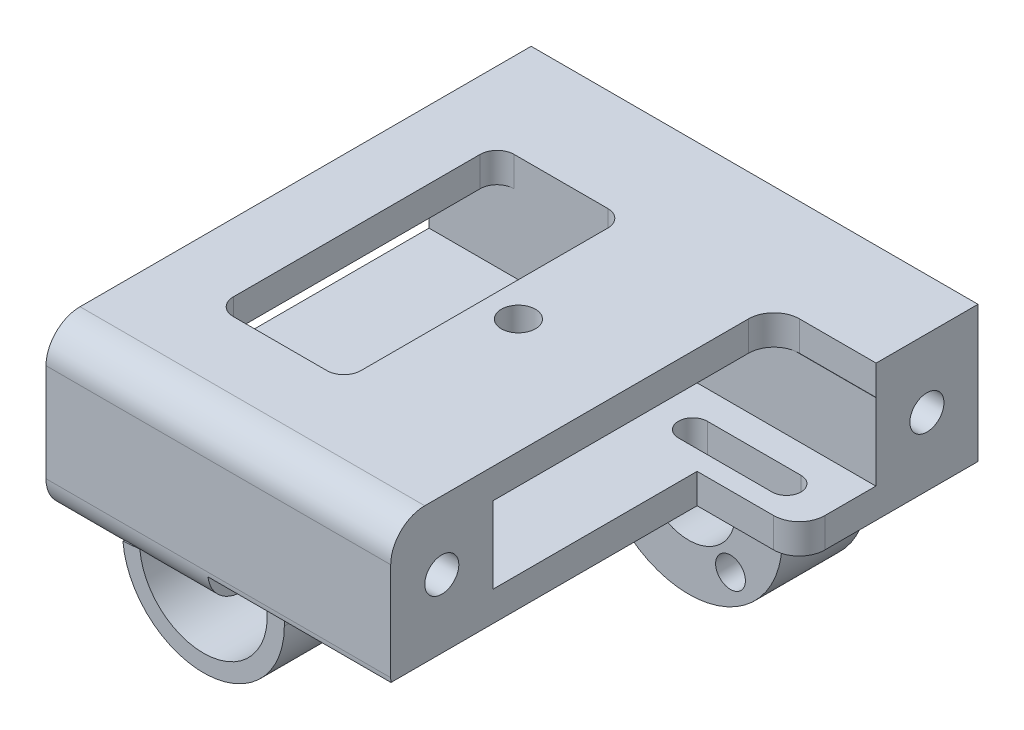
SolidWorks part; units mm, degrees
ref_plane "Front Plane" through (0, 0, 0) normal (0, 0, 1) x (1, 0, 0)
ref_plane "Top Plane" through (0, 0, 0) normal (0, 1, 0) x (1, 0, 0)
ref_plane "Right Plane" through (0, 0, 0) normal (1, 0, 0) x (0, 0, -1)
sketch "Sketch1" plane through (0, 0, 0) normal (0, 0, 1) x (1, 0, 0)
  line L0 (0, 0) -> (0, -35)
  line L1 (0, -35) -> (19, -35)
  line L2 (19, -35) -> (19, -16)
  line L3 (19, -16) -> (52.5, -16)
  line L4 (52.5, -16) -> (52.5, 0)
  line L5 (52.5, 0) -> (0, 0)
  line L6 (0, 0) -> (0.6966, -0.1385)
  dimension "D1" = 35
  dimension "D2" = 19
  dimension "D3" = 52.5
  dimension "D4" = 16
extrude "Boss-Extrude1" add sketch "Sketch1" along normal blind 57 contours L4 L5 L0 L1 L2 L3 region at (21.2152, -13.2602, 0)
ref_plane "Plane1" through (0, 0, 50) normal (0, 0, 1) x (1, 0, 0)
sketch "Sketch3" plane through (0, 0, 0) normal (-1, 0, 0) x (0, 0, 1)
  line L0 (57, 0) -> (0, 0) construction
  line L1 (12, -3.5) -> (45, -3.5)
  line L2 (12, -3.5) -> (12, -12.5)
  line L3 (12, -12.5) -> (45, -12.5)
  line L4 (45, -3.5) -> (45, -12.5)
  line L5 (57, -35) -> (48, -35)
  line L6 (57, -35) -> (57, -19.5)
  line L7 (57, -19.5) -> (48, -19.5)
  line L8 (48, -35) -> (48, -19.5)
  line L9 (0, 0) -> (0, -35) construction
  line L14 (57, -35) -> (0, -35) construction
  dimension "D1" = 9
  dimension "D2" = 33
  dimension "D3" = 3.5
  dimension "D4" = 12
  dimension "D5" = 15.5
  dimension "D6" = 9
extrude "Cut-Extrude2" cut sketch "Sketch3" against normal through all
fillet "Fillet1" radius 4 2 edges at (26.25, 0, 57) (9.5, -19.5, 57)
sketch "Sketch4" plane through (0, 0, 0) normal (0, 0, -1) x (-1, 0, 0)
  line L0 (-9.5, -25.5) -> (-9.5, -35) construction
  line L1 (0, -35) -> (-19, -35) construction
  line L2 (-2.0103, -25.1075) -> (-0.013, -25.0028)
  line L3 (0, -35) -> (-19, -35)
  line L4 (0, -35) -> (0, -16)
  line L5 (0, -16) -> (-19, -16)
  line L6 (-19, -35) -> (-19, -16)
  line L7 (-2.0285, -26.1537) -> (-0.0362, -26.328)
  line L8 (-2.0285, -26.1537) -> (-9.5, -25.5) construction
  line L9 (-0.013, -25.0028) -> (0, -25.0021)
  circle A0 centre (-9.5, -25.5) radius 7.5
  circle A1 centre (-9.5, -25.5) radius 9.5
  line M8 (-19, -35) -> (0, -35)
  line M9 (0, -35) -> (0, 0)
  dimension "D1" = 15
  dimension "D2" = 19
  dimension "D3" = 8
  dimension "D4" = 85
extrude "Cut-Extrude3" cut sketch "Sketch4" against normal through all contours A0 | A1 L6 M8 | L7 A1 L2 A0 | A1 L3 M9 | A1 L4 L9 region at (0.969, -25.6489, 0) region at (9.5, -25.5, 0) region at (0.0039, -25.1268, 0) region at (2.122, -32.878, 0) region at (16.878, -32.878, 0)
sketch "Sketch5" plane through (0, -16, 0) normal (0, -1, 0) x (1, 0, 0)
  line L0 (28, 28.5) -> (32, 28.5) construction
  line L1 (22, 45) -> (26, 45) construction
  line L2 (20, 43) -> (20, 14) construction
  line L3 (22, 12) -> (26, 12) construction
  line L4 (28, 43) -> (28, 14) construction
  line L5 (36, 17) -> (47, 17) construction
  line L6 (36, 18.7) -> (47, 18.7)
  line L7 (36, 15.3) -> (47, 15.3)
  line L8 (19, 56.9686) -> (19, 0) construction
  line L10 (19, 0) -> (52.5, 0) construction
  line L11 (52.5, 0) -> (52.5, 18) construction
  line L12 (52.5, 56.9686) -> (52.5, 0) construction
  line L13 (0, 57) -> (52.5, 57) construction
  line L14 (49.5, 18) -> (49.5, 21) construction
  line L15 (49.5, 21) -> (40.5, 21)
  line L16 (40.5, 21) -> (40.5, 57)
  line L18 (40.5, 57) -> (52.5, 57)
  line L19 (52.5, 57) -> (52.5, 18)
  arc A0 (20, 14) -> (22, 12) centre (22, 14) ccw construction
  arc A1 (26, 12) -> (28, 14) centre (26, 14) ccw construction
  arc A2 (28, 43) -> (26, 45) centre (26, 43) ccw construction
  arc A3 (22, 45) -> (20, 43) centre (22, 43) ccw construction
  circle A4 centre (32, 28.5) radius 2 construction
  arc A5 (36, 18.7) -> (36, 15.3) centre (36, 17) ccw
  arc A6 (47, 15.3) -> (47, 18.7) centre (47, 17) ccw
  arc A7 (52.5, 18) -> (49.5, 21) centre (49.5, 18) ccw
  point P17 (41.5, 17)
  line M12 (52.5, 0) -> (52.5, 56.9686)
  dimension "D1" = 2
  dimension "D4" = 4
  dimension "D6" = 1.7
  dimension "D9" = 2.3
  dimension "D12" = 6
  dimension "D2" = 8
  dimension "D3" = 33
  dimension "D5" = 4
  dimension "D7" = 11
  dimension "D8" = 1
  dimension "D10" = 12
  dimension "D11" = 18
  dimension "D13" = 9
  dimension "D14" = 4.5
extrude "Cut-Extrude4" cut sketch "Sketch5" against normal up to surface (12.5 mm away) contours A4 | L7 A6 L6 A5 | A7 L16 L15 M12 | L19 L18 L16 | L2 A0 L3 A1 L4 A2 L1 A3 region at (41.5, -16, 17) region at (46.5237, -16, 38.9169) up to face at (26.25, -3.5, 28.5)
sketch "Sketch6" plane through (0, 0, 0) normal (0, 1, 0) x (1, 0, 0)
  line L0 (52.5, 0) -> (0, 0) construction
  line L1 (10, -12) -> (21, -12)
  line L2 (8, -14) -> (8, -43)
  line L3 (10, -45) -> (21, -45)
  line L4 (23, -14) -> (23, -43)
  line L5 (0, -53) -> (0, 0) construction
  line L6 (52.5, -56.9686) -> (40.5, -56.9686) construction
  line L7 (43.5, -11.9686) -> (52.5, -11.9686)
  line L8 (40.5, -14.9686) -> (40.5, -56.9686)
  line L9 (40.5, -56.9686) -> (52.5, -56.9686)
  line L10 (52.5, -11.9686) -> (52.5, -56.9686)
  line L11 (52.5, -53) -> (52.5, 0) construction
  line L12 (27, -28.5) -> (23, -28.5) construction
  arc A0 (10, -45) -> (8, -43) centre (10, -43) cw
  arc A1 (23, -43) -> (21, -45) centre (21, -43) cw
  arc A2 (23, -14) -> (21, -12) centre (21, -14) ccw
  arc A3 (10, -12) -> (8, -14) centre (10, -14) ccw
  arc A4 (43.5, -11.9686) -> (40.5, -14.9686) centre (43.5, -14.9686) ccw
  circle A5 centre (27, -28.5) radius 2 construction
  point P6 (8, -45)
  point P11 (23, -12)
  point P14 (8, -12)
  point P25 (40.5, -11.9686)
  dimension "D3" = 2
  dimension "D8" = 3
  dimension "D9" = 4
  dimension "D10" = 4
  dimension "D1" = 33
  dimension "D2" = 15
  dimension "D4" = 12
  dimension "D5" = 8
  dimension "D6" = 45
  dimension "D7" = 12
extrude "Cut-Extrude5" cut sketch "Sketch6" against normal up to surface (3.5 mm away) up to face at (31, -3.5, 37.9895)
sketch "Sketch9" plane through (0, -3.5, 0) normal (0, -1, 0) x (1, 0, 0)
  line L0 (40.5, 21) -> (40.5, 56.9686) construction
  line L1 (19, 0) -> (52.5, 0) construction
  circle A0 centre (27, 28.5) radius 3.2
  dimension "D1" = 6.4
  dimension "D2" = 13.5
  dimension "D3" = 28.5
ref_plane "Plane3" through (0, -5, 0) normal (0, -1, 0) x (-1, 0, 0)
sketch "Sketch10" plane through (0, -5, 0) normal (0, -1, 0) x (-1, 0, 0)
  circle A0 centre (-27, -28.5) radius 2.8
  dimension "D1" = 5.6
loft "Loft1" add profiles "Sketch9", "Sketch10" connector at (30.0985, -3.5, 27.7003) connector at (29.7453, -5, 27.9494)
ref_plane "Plane4" through (0, -8, 0) normal (0, -1, 0) x (-1, 0, 0)
mirror "Mirror2" about plane through (0, -8, 0) normal (0, -1, 0) of "Loft1"
sketch "Sketch11" plane through (0, -11, 0) normal (0, 1, 0) x (1, 0, 0)
  circle A0 centre (27, -28.5) radius 2 construction
  circle A1 centre (27, -28.5) radius 2
extrude "Cut-Extrude6" cut sketch "Sketch11" against normal through all both and the other way through all
sketch "Sketch13" plane through (52.5, 0, 0) normal (1, 0, 0) x (0, 0, -1)
  line L0 (-51, -8) -> (-6, -8) construction
  line L1 (-6, -8) -> (0, -8) construction
  line L2 (0, -16) -> (0, 0) construction
  line L3 (-51, -8) -> (-57, -8) construction
  line L4 (-57, -4) -> (-57, -15.5) construction
  circle A0 centre (-6, -8) radius 2
  circle A1 centre (-51, -8) radius 2
  dimension "D1" = 45
  dimension "D2" = 4
extrude "Cut-Extrude7" cut sketch "Sketch13" against normal blind 20
sketch "Sketch14" plane through (0, 0, 0) normal (0, 0, -1) x (-1, 0, 0)
  line L0 (-28.5, -25.5) -> (-9.5, -25.5) construction
  line L1 (-28.5, -25.5) -> (-28.5, -14.5) construction
  line L2 (-23.5747, -19.1959) -> (-33.4253, -31.8041) construction
  line L3 (-34.8041, -20.5747) -> (-22.1959, -30.4253) construction
  line L4 (-28.5, -14.5) -> (-17.5, -14.5)
  line L5 (-17.5, -14.5) -> (-17.5, -25.5)
  circle A0 centre (-28.5, -25.5) radius 11
  circle A1 centre (-28.5, -25.5) radius 5.5
  circle A2 centre (-28.5, -25.5) radius 8 construction
  circle A3 centre (-23.5747, -19.1959) radius 1.75
  circle A4 centre (-34.8041, -20.5747) radius 1.75
  circle A5 centre (-33.4253, -31.8041) radius 1.75
  circle A6 centre (-22.1959, -30.4253) radius 1.75
  line M8 (-52.5, -16) -> (-19, -16)
  line M9 (-19, -16) -> (-19, -25.5)
  arc M10 (-19, -25.5) -> (-0.0362, -26.328) centre (-9.5, -25.5) ccw
  dimension "D1" = 19
  dimension "D2" = 22
  dimension "D3" = 11
  dimension "D4" = 38
  dimension "D5" = 3.5
  dimension "D6" = 16
extrude "Boss-Extrude2" add sketch "Sketch14" against normal blind 10 contours A0 A6 A5 A4 A3 A1 M9 M8 M10 | A0 M9 M8 region at (20.2019, -17.2019, 0) region at (20.9309, -17.9309, 0)
sketch "Sketch15" plane through (0, 0, 0) normal (-1, 0, 0) x (0, 0, 1)
  line L0 (53, 0) -> (0, 0) construction
  line L1 (53, -19.5) -> (48, -19.5)
  line L2 (57, -15.5) -> (57, -4)
  line L3 (53, 0) -> (48, 0)
  line L4 (48, -19.5) -> (48, 0)
  line L5 (57, -4) -> (57, -15.5) construction
  arc A0 (53, -19.5) -> (57, -15.5) centre (53, -15.5) ccw
  arc A1 (57, -4) -> (53, 0) centre (53, -4) ccw
  dimension "D1" = 4
sketch "Sketch16" plane through (0, 0, 0) normal (0, 0, -1) x (-1, 0, 0)
  line L0 (-28.5, -25.5) -> (-28.5, -31)
  line L1 (-33.4253, -31.8041) -> (-28.5, -25.5)
  circle A0 centre (-28.5, -25.5) radius 8
  circle A1 centre (-28.5, -25.5) radius 5.5 construction
  dimension "D1" = 38
